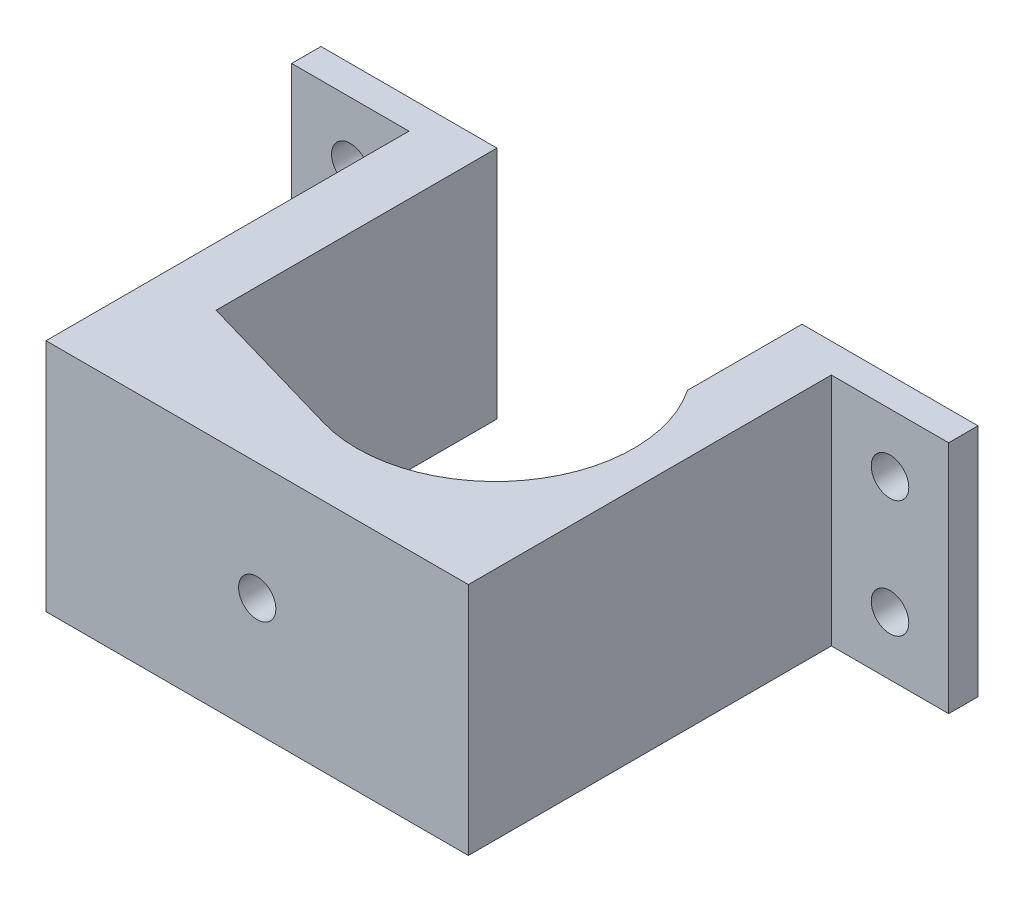
SolidWorks part; units mm, degrees
ref_plane "Front Plane" through (0, 0, 0) normal (0, 0, 1) x (1, 0, 0)
ref_plane "Top Plane" through (0, 0, 0) normal (0, 1, 0) x (1, 0, 0)
ref_plane "Right Plane" through (0, 0, 0) normal (1, 0, 0) x (0, 0, -1)
sketch "Sketch1" plane through (0, 0, 0) normal (0, 1, 0) x (1, 0, 0)
  line L0 (-20.574, -9.6521) -> (-4.162, -14.3967)
  line L1 (-4.1621, 14.3967) -> (-20.574, 9.652) construction
  line L2 (-20.574, 9.652) -> (-20.574, -9.6521)
  line L3 (-39.624, 20.7467) -> (-20.574, 20.7467)
  line L4 (-39.624, 20.7467) -> (-39.624, 17.5717)
  line L6 (12.446, 20.7467) -> (31.496, 20.7467)
  line L7 (-39.624, 17.5717) -> (-26.924, 17.5717)
  line L9 (-26.924, 17.5717) -> (-26.924, -12.8271)
  line L10 (31.496, 20.7467) -> (31.496, 17.5717)
  line L11 (31.496, 17.5717) -> (18.796, 17.5717)
  line L12 (18.796, 17.5717) -> (18.796, -12.8271)
  line L13 (-20.574, 9.652) -> (-20.574, 20.7467)
  line L14 (12.446, 20.7467) -> (12.446, 8.3478)
  line L15 (18.796, -12.8271) -> (18.796, -21.7171)
  line L16 (18.796, -21.7171) -> (-26.924, -21.7171)
  line L17 (-26.924, -21.7171) -> (-26.924, -12.8271)
  arc A0 (-4.162, -14.3967) -> (12.446, 8.3478) centre (0, 0) ccw
  arc A1 (-26.924, -12.8271) -> (18.796, -12.8271) centre (-4.064, 25.294) ccw construction
  arc A2 (12.446, 8.3478) -> (-4.1621, 14.3967) centre (0, 0) ccw construction
  point P6 (12.446, 14.5473)
  point P16 (21.971, 20.7467)
  dimension "D2" = 14.9863
  dimension "D14" = 6.35
  dimension "D10" = 44.45
  dimension "D1" = 19.3041
  dimension "D3" = 16.4119
  dimension "D4" = 106.124
  dimension "D5" = 20.574
  dimension "D6" = 106.125
  dimension "D7" = 6.35
  dimension "D8" = 6.35
  dimension "D9" = 3.175
  dimension "D11" = 12.7
  dimension "D12" = 3.175
  dimension "D13" = 33.02
  dimension "D15" = 8.89
extrude "Boss-Extrude1" add sketch "Sketch1" along normal blind 25.4
sketch "Sketch2" plane through (0, 0, -17.5717) normal (0, 0, 1) x (1, 0, 0)
  line L0 (-39.624, 0) -> (-26.924, 0) construction
  line L1 (-39.624, 25.4) -> (-39.624, 0) construction
  line L2 (-39.624, 25.4) -> (-26.924, 25.4) construction
  line L3 (31.496, 25.4) -> (31.496, 0) construction
  circle A0 centre (-33.274, 19.05) radius 2.032
  circle A1 centre (-33.274, 6.35) radius 2.032
  circle A2 centre (25.146, 19.05) radius 2.032
  circle A3 centre (25.146, 6.35) radius 2.032
  dimension "D5" = 4.064
  dimension "D1" = 6.35
  dimension "D2" = 6.35
  dimension "D3" = 6.35
  dimension "D4" = 6.35
extrude "Cut-Extrude1" cut sketch "Sketch2" against normal through all
sketch "Sketch3" plane through (0, 0, 21.7171) normal (0, 0, 1) x (1, 0, 0)
  line L0 (-26.924, 25.4) -> (18.796, 25.4) construction
  line L1 (-26.924, 25.4) -> (-26.924, 0) construction
  circle A0 centre (-4.064, 12.7) radius 1.905
  point P2 (0, 0)
  dimension "D3" = 3.81
  dimension "D1" = 12.7
  dimension "D2" = 22.86
hole_wizard "#10-32 Tapped Hole1" positions "Sketch4" profile "Sketch5" tap size "#10-32" standard "ANSI Inch" end condition through all
sketch "Sketch4" plane through (0, 0, 21.7171) normal (0, 0, 1) x (1, 0, 0)
  point P0 (-4.064, 12.7)
  point P4 (-4.064, 12.7)
sketch "Sketch5" plane through (-4.064, 12.7, 21.7171) normal (1, 0, 0) x (0, -1, 0)
  line L0 (0, 0) -> (0, 42.4638)
  line L1 (0, 42.4638) -> (2.0193, 42.4638)
  line L2 (2.0193, 42.4638) -> (2.0193, 0)
  line L5 (2.0193, 0) -> (0, 0)
  line L11 (0, -6.35) -> (0, 107.95) construction
  dimension "Thru Tap Drill Dia." = 4.0386
  dimension "Thru Tap Drill Depth" = 42.4638
cosmetic thread "Hole Thread1" parameters "D2"=4.826
